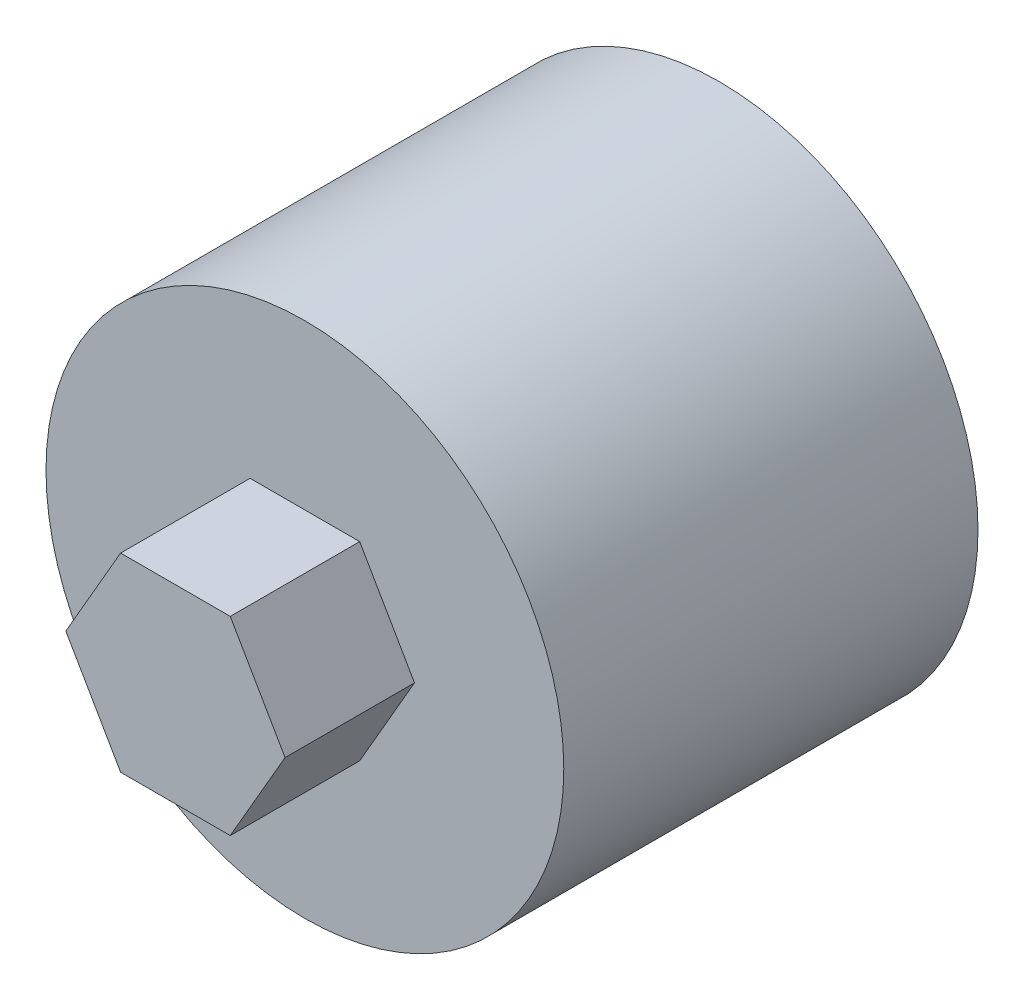
SolidWorks part; units mm, degrees
ref_plane "前视基准面" through (0, 0, 0) normal (0, 0, 1) x (1, 0, 0)
ref_plane "上视基准面" through (0, 0, 0) normal (0, 1, 0) x (1, 0, 0)
ref_plane "右视基准面" through (0, 0, 0) normal (1, 0, 0) x (0, 0, -1)
other "Configuration Table"
sketch "草图1" plane through (0, 0, 0) normal (0, 0, 1) x (1, 0, 0)
  line L0 (0, 0) -> (1.6914, 0.6156) construction
  line L1 (0, 0) -> (1.5832, 0.5954)
  line L2 (0, 0) -> (1.5832, -0.5954)
  line L3 (0, 0) -> (1.6914, -0.6156) construction
  line L4 (0, 0) -> (2.55, 0) construction
  line L5 (1.6914, 0.6156) -> (1.6914, -0.6156) construction
  circle A0 centre (0, 0) radius 1.65
  circle A1 centre (0, 0) radius 2.55
  circle A2 centre (0, 0) radius 1.6914 construction
  circle A3 centre (0, 0) radius 1.8 construction
  circle A4 centre (0, 0) radius 3
  spline S0 degree 4 poles (1.5832, 0.5954) (1.5953, 0.5999) (1.6299, 0.61) (1.6985, 0.6188) (1.8107, 0.6176) (1.9542, 0.5935) (2.1323, 0.5368) (2.3288, 0.4397) (2.527, 0.3033) (2.7182, 0.1281) (2.8863, -0.0692) (3.0309, -0.2841) (3.1583, -0.5243) (3.284, -0.8365) (3.3855, -1.2255) (3.4358, -1.6902) (3.4119, -2.2085) (3.3126, -2.7182) (3.1474, -3.2089) (2.918, -3.6756) (2.6387, -4.1089) (2.3029, -4.5102) (1.9385, -4.866) (1.5141, -5.1906) (1.1742, -5.4065) (0.7714, -5.6132) (0.5343, -5.7151) (0.2601, -5.8236) (0.1183, -5.8645) (-0.005, -5.9055) (-0.0434, -5.9147) (-0.0704, -5.9226) (-0.0848, -5.927) knots 0 0 0 0 0 0.005604 0.015718 0.02996 0.048734 0.068727 0.096889 0.125051 0.153212 0.181374 0.209535 0.237696 0.271429 0.327752 0.384075 0.440398 0.496721 0.553044 0.609367 0.66569 0.722013 0.778336 0.834659 0.890982 0.909091 0.954545 0.977273 0.988636 0.994318 1 1 1 1 1 construction
  spline S1 degree 4 poles (1.5832, 0.5954) (1.5953, 0.5999) (1.6299, 0.61) (1.6985, 0.6188) (1.8107, 0.6176) (1.9542, 0.5935) (2.1323, 0.5368) (2.3288, 0.4397) (2.527, 0.3033) (2.7182, 0.1281) (2.8863, -0.0692) (3.0309, -0.2841) (3.1583, -0.5243) (3.284, -0.8365) (3.3855, -1.2255) (3.4358, -1.6902) (3.4119, -2.2085) (3.3126, -2.7182) (3.1474, -3.2089) (2.918, -3.6756) (2.6387, -4.1089) (2.3029, -4.5102) (1.9385, -4.866) (1.5141, -5.1906) (1.1742, -5.4065) (0.8753, -5.5599) (0.734, -5.626) (0.6996, -5.6416) knots 0 0 0 0 0 0.005604 0.015718 0.02996 0.048734 0.068727 0.096889 0.125051 0.153212 0.181374 0.209535 0.237696 0.271429 0.327752 0.384075 0.440398 0.496721 0.553044 0.609367 0.66569 0.722013 0.778336 0.834659 0.890982 0.909091 0.909091 0.909091 0.909091 0.909091
  spline S2 degree 4 poles (1.5832, -0.5954) (1.5953, -0.5999) (1.6299, -0.61) (1.6985, -0.6188) (1.8107, -0.6176) (1.9542, -0.5935) (2.1323, -0.5368) (2.3288, -0.4397) (2.527, -0.3033) (2.7182, -0.1281) (2.8863, 0.0692) (3.0309, 0.2841) (3.1583, 0.5243) (3.284, 0.8365) (3.3855, 1.2255) (3.4358, 1.6902) (3.4119, 2.2085) (3.3126, 2.7182) (3.1474, 3.2089) (2.918, 3.6756) (2.6387, 4.1089) (2.3029, 4.5102) (1.9385, 4.866) (1.5141, 5.1906) (1.1742, 5.4065) (0.7714, 5.6132) (0.5343, 5.7151) (0.2601, 5.8236) (0.1183, 5.8645) (-0.005, 5.9055) (-0.0434, 5.9147) (-0.0704, 5.9226) (-0.0848, 5.927) knots 0 0 0 0 0 0.005604 0.015718 0.02996 0.048734 0.068727 0.096889 0.125051 0.153212 0.181374 0.209535 0.237696 0.271429 0.327752 0.384075 0.440398 0.496721 0.553044 0.609367 0.66569 0.722013 0.778336 0.834659 0.890982 0.909091 0.954545 0.977273 0.988636 0.994318 1 1 1 1 1 construction
  spline S3 degree 4 poles (1.5832, -0.5954) (1.5953, -0.5999) (1.6299, -0.61) (1.6985, -0.6188) (1.8107, -0.6176) (1.9542, -0.5935) (2.1323, -0.5368) (2.3288, -0.4397) (2.527, -0.3033) (2.7182, -0.1281) (2.8863, 0.0692) (3.0309, 0.2841) (3.1583, 0.5243) (3.284, 0.8365) (3.3855, 1.2255) (3.4358, 1.6902) (3.4119, 2.2085) (3.3126, 2.7182) (3.1474, 3.2089) (2.918, 3.6756) (2.6387, 4.1089) (2.3029, 4.5102) (1.9385, 4.866) (1.5141, 5.1906) (1.1742, 5.4065) (0.8753, 5.5599) (0.734, 5.626) (0.6996, 5.6416) knots 0 0 0 0 0 0.005604 0.015718 0.02996 0.048734 0.068727 0.096889 0.125051 0.153212 0.181374 0.209535 0.237696 0.271429 0.327752 0.384075 0.440398 0.496721 0.553044 0.609367 0.66569 0.722013 0.778336 0.834659 0.890982 0.909091 0.909091 0.909091 0.909091 0.909091
  point P16 (1.6914, 0)
  dimension "内啮合齿顶圆直径" = 3.3
  dimension "内啮合分度圆直径" = 3.6
  dimension "内啮合基圆直径" = 3.3829
  dimension "内啮合齿根圆直径" = 5.1
  dimension "外径" = 6
  dimension "渐开线镜像线夹角" = 20
extrude "凸台-拉伸1" add sketch "草图1" along normal blind 4 contours A4 | A0
extrude "切除-拉伸2" cut sketch "草图1<3>" along normal through all contours A0 S3 A1 S1 region at (2.0287, 0, 0)
sketch "草图1<3>" plane through (0, 0, 0) normal (0, 0, 1) x (1, 0, 0) same geometry as "草图1"
pattern_circular "阵列(圆周)1" count 9 over 360 about axis through (0, 0, 4) along (0, 0, 1) of "切除-拉伸2"
sketch "草图2" plane through (0, 0, 4) normal (0, 0, 1) x (1, 0, 0)
  line L1 (0.6351, 1.1) -> (-0.6351, 1.1)
  line L2 (-0.6351, 1.1) -> (-1.2702, 0)
  line L3 (-1.2702, 0) -> (-0.6351, -1.1)
  line L4 (-0.6351, -1.1) -> (0.6351, -1.1)
  line L5 (0.6351, -1.1) -> (1.2702, 0)
  line L6 (1.2702, 0) -> (0.6351, 1.1)
  circle A0 centre (0, 0) radius 3
  circle A1 centre (0, 0) radius 3 construction
  circle A2 centre (0, 0) radius 1.2702
  circle A3 centre (0, 0) radius 1.1 construction
  dimension "D1" = 2.2
extrude "凸台-拉伸2" add sketch "草图2" along normal blind 0.8 contours A0
extrude "凸台-拉伸3" add sketch "草图2<3>" along normal blind 1.5 from surface contours L1 L2 L3 L4 L5 L6 starting at face at (3, 0, 4.8)
sketch "草图2<3>" plane through (0, 0, 4) normal (0, 0, 1) x (1, 0, 0) same geometry as "草图2"
extrude "凸台-拉伸4" add sketch "草图2<4>" against normal blind 4 contours A0
sketch "草图2<4>" plane through (0, 0, 4) normal (0, 0, 1) x (1, 0, 0) same geometry as "草图2"
sketch "草图3" plane through (0, 0, 0) normal (0, 0, -1) x (-1, 0, 0)
  line L0 (1.1, 1.092) -> (1.1, -1.092)
  circle A0 centre (0, 0) radius 1.55
  dimension "D1" = 3.1
  dimension "D2" = 1.1
extrude "切除-拉伸3" cut sketch "草图3" against normal offset from surface (3.8 mm away) 1 contours L0 A0 region at (0.1264, 0, 0) up to face at (3, 0, 4.8)
equation "\"m\"= 0.4'模数"
equation "\"z1\"= 6'外啮合齿轮数"
equation "\"a\"= 20度'压力角"
equation "\"z2\"= 9'内啮合齿轮数"
equation "\"hax\"= 1'齿顶高系数"
equation "\"cx\"= 0.25'顶隙系数"
equation "\"ha\"= \"hax\" * \"m\"'齿顶高"
equation "\"hf\"= ( \"hax\" + \"cx\" ) * \"m\"'齿根高"
equation "\"d1\"= \"m\" * \"z1\"'外啮合分度圆直径"
equation "\"da1\"= ( \"z1\" + 2 ) * \"m\"'外啮合齿顶圆直径"
equation "\"df1\"= \"d1\" - 2 * \"hf\"'外啮合齿根圆直径"
equation "\"db1\"= \"d1\" * cos ( \"a\" )'外啮合基圆直径"
equation "\"p\"= \"m\" * PI'齿距"
equation "\"d2\"= \"m\" * \"z2\"'内啮合分度圆直径"
equation "\"db2\"= \"d2\" * cos ( \"a\" )'内啮合基圆直径"
equation "\"da2\"= ( \"z2\" - 2 ) * \"m\"'内啮合齿顶圆直径"
equation "\"df2\"= \"d2\" + 2 * \"hf\"'内啮合齿根圆直径"
equation "\"内啮合齿顶圆直径@草图1\" = \"da2\" + 1 * \"hf\""
equation "\"内啮合齿根圆直径@草图1\" = \"df2\" + 1 * \"hf\""
equation "\"内啮合分度圆直径@草图1\"= \"d2\""
equation "\"内啮合基圆直径@草图1\"= \"db2\""
equation "\"渐开线镜像线夹角@草图1\" = 360度 / 4 / \"z2\" + 360度 / 4 / \"z2\""
equation "\"do\"= IIF ( \"edo\" >= ( \"df2\" + 1 ) , \"edo\" , ( \"df2\" + 1 ) )'外圈直径"
equation "\"h\"= 4'厚度"
equation "\"外径@草图1\"= \"do\""
equation "\"厚度@凸台-拉伸1\"= \"h\""
equation "\"内啮合齿轮数@阵列(圆周)1\"= \"z2\""
equation "\"edo\"= 6'期望的外圈直径"
